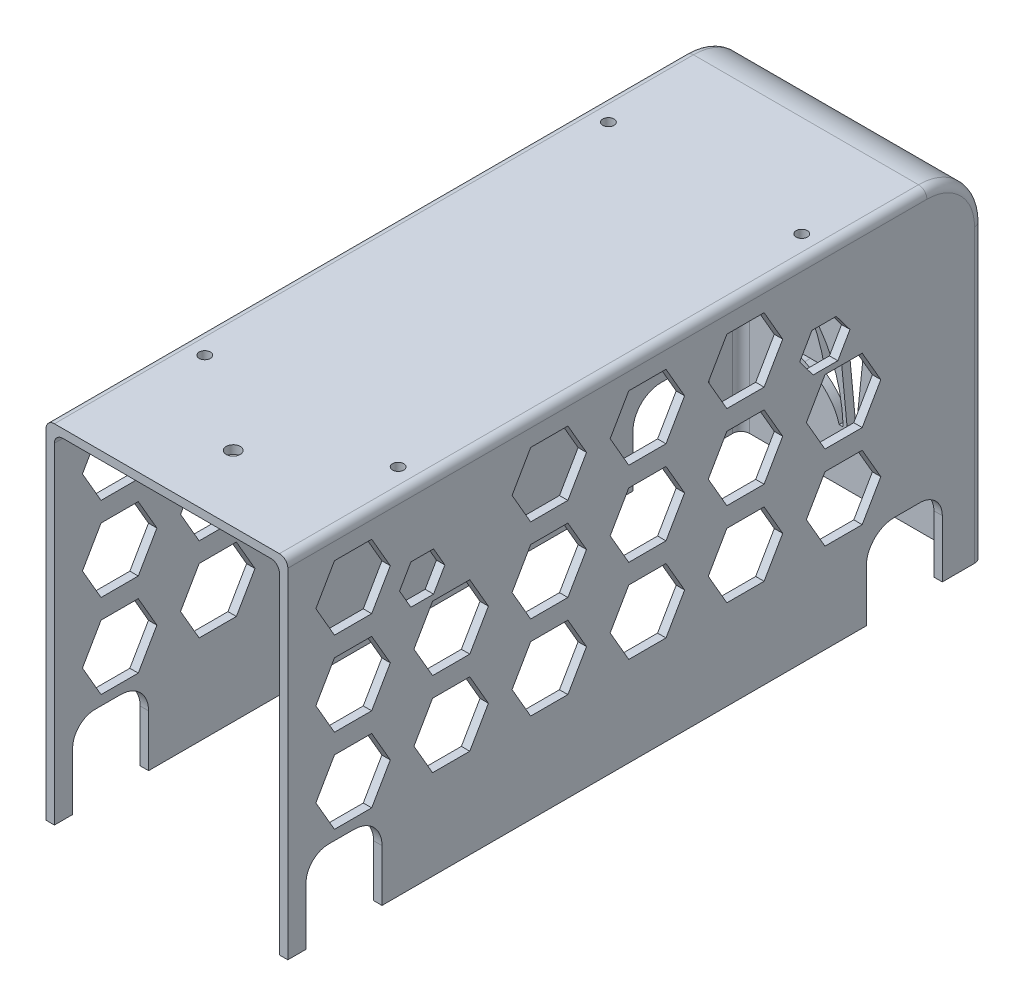
SolidWorks part; units mm, degrees
ref_plane "Front Plane" through (0, 0, 0) normal (0, 0, 1) x (1, 0, 0)
ref_plane "Top Plane" through (0, 0, 0) normal (0, 1, 0) x (1, 0, 0)
ref_plane "Right Plane" through (0, 0, 0) normal (1, 0, 0) x (0, 0, -1)
sketch "Sketch1" plane through (0, 0, 0) normal (1, 0, 0) x (0, 0, -1)
  line L0 (-77.887, -82.1549) -> (77.913, -82.1549)
  line L1 (-124.987, 51.8451) -> (125.013, 51.8451)
  line L2 (-124.987, 51.8451) -> (-124.987, -82.1549)
  line L3 (-124.987, -82.1549) -> (-94.887, -82.1549)
  line L4 (125.013, 51.8451) -> (125.013, -82.1549)
  line L15 (0.013, 51.8451) -> (0.013, -82.1549) construction
  line L16 (94.913, -82.1549) -> (125.013, -82.1549)
  line L17 (-94.887, -82.1549) -> (-77.887, -82.1549) construction
  line L18 (-94.887, -82.1549) -> (-94.887, -78.1549)
  line L20 (-77.887, -78.1549) -> (-77.887, -82.1549)
  line L21 (77.913, -78.1549) -> (77.913, -82.1549)
  line L22 (94.913, -82.1549) -> (94.913, -78.1549)
  circle A6 centre (-101.987, -28.6549) radius 10
  circle A7 centre (102.013, -28.6549) radius 10
  arc A10 (-77.887, -78.1549) -> (-94.887, -78.1549) centre (-86.387, -78.1549) ccw
  arc A11 (77.913, -78.1549) -> (94.913, -78.1549) centre (86.413, -78.1549) cw
  dimension "D3" = 4
  dimension "D7" = 23
  dimension "D8" = 20
  dimension "D9" = 53.5
  dimension "D4" = 17
  dimension "D1" = 250
  dimension "D2" = 134
extrude "Boss-Extrude1" add sketch "Sketch1" against normal blind 3
sketch "Sketch2" plane through (-3, 0, 0) normal (-1, 0, 0) x (0, 0, 1)
  line L0 (-125.013, 51.8451) -> (-72.013, 51.8451) construction
  line L1 (-125.013, 51.8451) -> (124.987, 51.8451) construction
  line L2 (-72.013, 51.8451) -> (-72.013, 59.8451) construction
  line L3 (-0.013, 51.8451) -> (-0.013, -82.1549) construction
  line L4 (-75.013, 59.8451) -> (-69.013, 59.8451)
  line L5 (-76.013, 58.8451) -> (-76.013, 54.8451)
  line L6 (-75.013, 53.8451) -> (-69.013, 53.8451)
  line L7 (-68.013, 58.8451) -> (-68.013, 54.8451)
  line L8 (77.887, -82.1549) -> (-77.913, -82.1549) construction
  line L9 (71.987, 51.8451) -> (71.987, 59.8451) construction
  line L10 (124.987, 51.8451) -> (71.987, 51.8451) construction
  line L11 (67.987, 58.8451) -> (67.987, 54.8451)
  line L12 (74.987, 53.8451) -> (68.987, 53.8451)
  line L13 (75.987, 58.8451) -> (75.987, 54.8451)
  line L14 (74.987, 59.8451) -> (68.987, 59.8451)
  arc A0 (-69.013, 59.8451) -> (-68.013, 58.8451) centre (-69.013, 58.8451) cw
  arc A1 (-69.013, 53.8451) -> (-68.013, 54.8451) centre (-69.013, 54.8451) ccw
  arc A2 (-76.013, 54.8451) -> (-75.013, 53.8451) centre (-75.013, 54.8451) ccw
  arc A3 (-75.013, 59.8451) -> (-76.013, 58.8451) centre (-75.013, 58.8451) ccw
  arc A4 (74.987, 59.8451) -> (75.987, 58.8451) centre (74.987, 58.8451) cw
  arc A5 (75.987, 54.8451) -> (74.987, 53.8451) centre (74.987, 54.8451) cw
  arc A6 (68.987, 53.8451) -> (67.987, 54.8451) centre (68.987, 54.8451) cw
  arc A7 (68.987, 59.8451) -> (67.987, 58.8451) centre (68.987, 58.8451) ccw
  point P10 (-72.013, 59.8451)
  point P17 (-76.013, 53.8451)
  point P20 (-76.013, 59.8451)
  point P40 (75.987, 59.8451)
  point P41 (75.987, 53.8451)
  dimension "D5" = 1
  dimension "D1" = 53
  dimension "D2" = 2
  dimension "D3" = 8
extrude "Boss-Extrude2" add sketch "Sketch2" along normal blind 10
sketch "Sketch3" plane through (0, 59.8451, 0) normal (0, 1, 0) x (1, 0, 0)
  line L3 (-3, 0.013) -> (-19.4349, 0.013) construction
  line L4 (-3, 125.013) -> (-3, -124.987) construction
  line L5 (-13, -71.987) -> (-3, -71.987) construction
  circle A0 centre (-8.6365, 72.013) radius 1.7353
  circle A1 centre (-8.6365, -71.987) radius 1.7353
sketch "Sketch4" plane through (0, 53.8451, 0) normal (0, -1, 0) x (1, 0, 0)
  line L0 (-13, -72.013) -> (-3, -72.013) construction
  line L14 (-13, -75.013) -> (-13, -69.013) construction
  line L15 (-3, -75.013) -> (-3, -69.013) construction
  line L16 (-3, 71.987) -> (-13, 71.987) construction
  line L17 (-3, 68.987) -> (-3, 74.987) construction
  line L18 (-13, 68.987) -> (-13, 74.987) construction
  line L19 (-8.6365, 71.987) -> (-8.6365, -72.013) construction
  circle A1 centre (-8.6365, 71.987) radius 3
  circle A3 centre (-8.6365, -72.013) radius 3
  dimension "D1" = 6
  dimension "D2" = 6
sketch "Sketch5" plane through (0, 0, 0) normal (1, 0, 0) x (0, 0, -1)
  line L1 (-124.987, 51.8451) -> (125.013, 51.8451)
  line L2 (-124.987, 51.8451) -> (-124.987, 76.8451)
  line L10 (0.013, 76.8451) -> (0.013, -82.1549) construction
  line L11 (-77.887, -82.1549) -> (77.913, -82.1549) construction
  line L12 (0.013, -2.6549) -> (173.6231, -2.6549) construction
  line L21 (125.013, 51.8451) -> (125.013, -82.1549)
  line L23 (-124.987, 76.8451) -> (108.013, 76.8451)
  line L24 (128.013, 56.8451) -> (128.013, -82.1549)
  line L25 (128.013, -82.1549) -> (125.013, -82.1549)
  arc A8 (108.013, 76.8451) -> (128.013, 56.8451) centre (108.013, 56.8451) cw
  line M30 (125.013, -82.1549) -> (125.013, 51.8451)
  line M31 (125.013, 51.8451) -> (-124.987, 51.8451)
  dimension "D2" = 3
  dimension "D1" = 20
extrude "Boss-Extrude3" add sketch "Sketch5" against normal up to surface (3 mm away) contours L2 M30 M31 region at (0, 59.429, -7.5021) up to face at (-3, -28.6549, -92.013)
sketch "Sketch6" plane through (0, 76.8451, 0) normal (0, 1, 0) x (1, 0, 0)
  line L2 (-83.2765, 76.013) -> (-73.2765, 76.013) construction
  line L3 (-83.2765, 76.013) -> (-83.2765, 68.9594) construction
  line L4 (-83.2765, 68.9594) -> (-73.2765, 68.9594) construction
  line L5 (-73.2765, 76.013) -> (-73.2765, 68.9594) construction
  line L6 (-13, 76.013) -> (-3, 76.013) construction
  line L7 (-13, 76.013) -> (-13, 68.013) construction
  line L10 (-83.2765, -124.987) -> (-86.2765, -124.987)
  line L14 (-8.6365, 0.013) -> (-65.4749, 0.013) construction
  line L15 (-73.2765, -75.987) -> (-73.2765, -68.9334) construction
  line L16 (-83.2765, -68.9334) -> (-73.2765, -68.9334) construction
  line L17 (-83.2765, -75.987) -> (-83.2765, -68.9334) construction
  line L18 (-83.2765, -75.987) -> (-73.2765, -75.987) construction
  line L19 (-83.2765, 128.013) -> (-86.2765, 128.013)
  line L23 (-83.2765, 128.013) -> (-83.2765, -124.987)
  line L24 (-86.2765, -124.987) -> (-86.2765, 128.013)
  line L26 (-86.2765, 135.013) -> (-113.3718, 135.013) construction
  circle A1 centre (-77.6365, 72.013) radius 1.735 construction
  circle A6 centre (-77.6365, -71.987) radius 1.735 construction
  dimension "D2" = 3.47
  dimension "D3" = 4
  dimension "D4" = 5.64
  dimension "D5" = 10
extrude "Boss-Extrude4" add sketch "Sketch6" against normal up to surface (159 mm away) separate body up to face at (-1.5, -82.1549, -111.463)
sketch "Sketch8" plane through (-83.2765, 0, 0) normal (-1, 0, 0) x (0, 0, 1)
  line L0 (-75.013, 59.8451) -> (-69.013, 59.8451)
  line L1 (-68.013, 58.8451) -> (-68.013, 54.8451)
  line L2 (-69.013, 53.8451) -> (-75.013, 53.8451)
  line L3 (-76.013, 54.8451) -> (-76.013, 58.8451)
  line L4 (68.987, 59.8451) -> (74.987, 59.8451)
  line L5 (75.987, 58.8451) -> (75.987, 54.8451)
  line L6 (74.987, 53.8451) -> (68.987, 53.8451)
  line L7 (67.987, 54.8451) -> (67.987, 58.8451)
  arc A0 (-69.013, 59.8451) -> (-68.013, 58.8451) centre (-69.013, 58.8451) cw
  arc A1 (-68.013, 54.8451) -> (-69.013, 53.8451) centre (-69.013, 54.8451) cw
  arc A2 (-75.013, 53.8451) -> (-76.013, 54.8451) centre (-75.013, 54.8451) cw
  arc A3 (-76.013, 58.8451) -> (-75.013, 59.8451) centre (-75.013, 58.8451) cw
  arc A4 (74.987, 59.8451) -> (75.987, 58.8451) centre (74.987, 58.8451) cw
  arc A5 (75.987, 54.8451) -> (74.987, 53.8451) centre (74.987, 54.8451) cw
  arc A6 (68.987, 53.8451) -> (67.987, 54.8451) centre (68.987, 54.8451) cw
  arc A7 (67.987, 58.8451) -> (68.987, 59.8451) centre (68.987, 58.8451) cw
extrude "Boss-Extrude6" add sketch "Sketch8" against normal blind 10
sketch "Sketch9" plane through (0, 59.8451, 0) normal (0, 1, 0) x (1, 0, 0)
  line L0 (-83.2765, 72.013) -> (-3, 72.013) construction
  line L1 (-83.2765, 69.013) -> (-83.2765, 75.013) construction
  line L2 (-3, 69.013) -> (-3, 75.013) construction
  line L3 (-43.1383, 72.013) -> (-43.1383, -18.9939) construction
  circle A0 centre (-77.6365, -71.987) radius 1.735
  circle A1 centre (-77.6365, 72.013) radius 1.735
  circle A2 centre (-8.64, -71.987) radius 1.735
  circle A3 centre (-8.64, 72.013) radius 1.735
  dimension "D1" = 3.47
extrude "Cut-Extrude3" cut sketch "Sketch9" against normal blind 10
sketch "Sketch11" plane through (-3, 0, 0) normal (-1, 0, 0) x (0, 0, 1)
  line L5 (124.987, 73.8451) -> (124.987, 76.8451)
  line L6 (-125.013, -82.1549) -> (-128.013, -82.1549)
  line L7 (-125.013, 56.8451) -> (-125.013, -82.1549)
  line L8 (124.987, 73.8451) -> (-108.013, 73.8451)
  line L9 (-125.013, 56.8451) -> (-125.013, -82.1549)
  line L10 (124.987, 73.8451) -> (-108.013, 73.8451)
  line L11 (-128.013, -82.1549) -> (-128.013, 56.8451)
  line L12 (-108.013, 76.8451) -> (124.987, 76.8451)
  arc A2 (-128.013, 56.8451) -> (-108.013, 76.8451) centre (-108.013, 56.8451) cw
  arc A3 (-108.013, 73.8451) -> (-125.013, 56.8451) centre (-108.013, 56.8451) ccw
  arc A4 (-108.013, 73.8451) -> (-125.013, 56.8451) centre (-108.013, 56.8451) ccw
  dimension "D1" = 3
extrude "Boss-Extrude7" add sketch "Sketch11" along normal up to surface (80.2765 mm away) up to face at (-83.2765, 56.8451, 71.987)
sketch "Sketch13" plane through (0, 0, 0) normal (1, 0, 0) x (0, 0, -1)
  line L0 (-111.987, -28.6549) -> (-111.987, -82.1549)
  line L1 (-124.987, -82.1549) -> (-94.887, -82.1549) construction
  line L7 (94.913, -82.1549) -> (128.013, -82.1549) construction
  line L8 (112.013, -82.1549) -> (112.013, -28.6549)
  line L10 (-77.887, -78.1549) -> (-77.887, -82.1549) construction
  line L16 (-101.987, -18.6549) -> (-96.387, -18.6549)
  line L17 (-86.387, -28.6549) -> (-86.387, -69.6549)
  line L18 (102.013, -18.6549) -> (96.413, -18.6549)
  line L19 (86.413, -28.6549) -> (86.413, -69.6549)
  line L21 (-77.887, -78.1549) -> (-77.887, -82.1549)
  line L22 (-77.887, -82.1549) -> (-111.987, -82.1549)
  line L24 (77.913, -78.1549) -> (77.913, -82.1549)
  line L25 (-124.987, -82.1549) -> (125.013, -82.1549) construction
  line L26 (77.913, -82.1549) -> (112.013, -82.1549)
  arc A0 (-101.987, -18.6549) -> (-111.987, -28.6549) centre (-101.987, -28.6549) ccw
  arc A1 (112.013, -28.6549) -> (102.013, -18.6549) centre (102.013, -28.6549) ccw
  arc A2 (-86.387, -69.6549) -> (-77.887, -78.1549) centre (-86.387, -78.1549) cw
  arc A3 (77.913, -78.1549) -> (86.413, -69.6549) centre (86.413, -78.1549) cw
  arc A4 (-96.387, -18.6549) -> (-86.387, -28.6549) centre (-96.387, -28.6549) cw
  arc A5 (96.413, -18.6549) -> (86.413, -28.6549) centre (96.413, -28.6549) ccw
  dimension "D1" = 10
  dimension "D2" = 10
extrude "Cut-Extrude6" cut sketch "Sketch13" against normal blind 143
sketch "Sketch14" plane through (0, 0, 0) normal (1, 0, 0) x (0, 0, -1)
  line L1 (-124.987, -82.1549) -> (128.013, -82.1549)
  line L2 (-124.987, -82.1549) -> (-124.987, -47.1549)
  line L7 (-124.987, -47.1549) -> (128.013, -47.1549)
  line L8 (128.013, -82.1549) -> (128.013, -47.1549)
  line L9 (128.013, 56.8451) -> (128.013, -82.1549) construction
  dimension "D1" = 35
extrude "Cut-Extrude7" cut sketch "Sketch14" against normal blind 143
sketch "Sketch15" plane through (0, 0, 0) normal (1, 0, 0) x (0, 0, -1)
  line L8 (108.013, 76.8451) -> (128.013, 76.8451)
  line L9 (128.013, 76.8451) -> (128.013, 56.8451)
  line L14 (128.013, 56.8451) -> (128.013, -47.1549) construction
  line L15 (128.013, 56.8451) -> (128.013, 76.8451) construction
  arc A1 (128.013, 56.8451) -> (108.013, 76.8451) centre (108.013, 56.8451) ccw
extrude "Cut-Extrude8" cut sketch "Sketch15" against normal blind 143
fillet "Fillet3" radius 3 3 edges at (0, 4.8451, -128.013) (0, 70.9872, -122.1551) (0, 76.8451, 8.487)
fillet "Fillet4" radius 3 3 edges at (-86.2765, 76.8451, 8.487) (-86.2765, 4.8451, -128.013) (-86.2765, 70.9872, -122.1551)
fillet "Fillet5" radius 3 6 edges at (-3, 4.8451, -125.013) (-3, 68.8659, -120.0338) (-83.2765, 4.8451, -125.013) (-83.2765, 68.8659, -120.0338) (-3, 73.8451, 8.487) (-83.2765, 73.8451, 8.487)
sketch "Sketch17" plane through (0, 76.8451, 0) normal (0, 1, 0) x (1, 0, 0)
  circle A3 centre (-43.1388, -96.337) radius 2.5
  dimension "D6" = 5
extrude "Cut-Extrude9" cut sketch "Sketch17" against normal blind 143
sketch "Sketch18" plane through (0, 0, 0) normal (1, 0, 0) x (0, 0, -1)
  line L1 (-132.5686, 81.0343) -> (-119.987, 81.0343)
  line L2 (-132.5686, 81.0343) -> (-132.5686, -50.9934)
  line L3 (-132.5686, -50.9934) -> (-119.987, -50.9934)
  line L4 (-119.987, 81.0343) -> (-119.987, -50.9934)
extrude "Cut-Extrude10" cut sketch "Sketch18" against normal blind 143
sketch "Sketch21" plane through (0, 0, -128.013) normal (0, 0, -1) x (-1, 0, 0)
  line L0 (3, 56.8451) -> (3, -47.1549) construction
  line L1 (83.2765, -47.1549) -> (83.2765, 56.8451) construction
  arc A0 (3, 23.6188) -> (83.2765, 23.6188) centre (43.1383, -11.0736) cw construction
  text T0 "SOKA UNVERSITY" font "Arial Narrow" height in points 26
extrude "Cut-Extrude11" cut sketch "Sketch21" against normal blind 143
sketch "Sketch22" plane through (0, 0, -128.013) normal (0, 0, -1) x (-1, 0, 0)
  line L0 (-62.3867, -52.9922) -> (58.1402, -52.9922) construction
  line L1 (42.401, -28.4273) -> (45.401, -28.4273)
  line L2 (45.401, -28.4273) -> (48.0456, -3.2659)
  line L3 (48.0456, -3.2659) -> (45.049, 3.6095)
  line L7 (42.7531, 3.6095) -> (39.7564, -3.2659)
  line L8 (39.7564, -3.2659) -> (42.401, -28.4273)
  line L9 (53.5774, -13.0804) -> (67.6449, -13.0804)
  line L10 (43.901, -28.4273) -> (43.901, -11.0471) construction
  line L11 (34.2246, -13.0804) -> (20.1572, -13.0804)
  line L12 (39.501, -28.4313) -> (40.901, -28.4313)
  line L13 (46.901, -28.4313) -> (48.301, -28.4313)
  line L14 (42.7531, 3.6095) -> (42.7531, -3.2659)
  line L15 (42.7531, -3.2659) -> (45.049, -3.2659)
  line L16 (45.049, -3.2659) -> (45.049, 3.6095)
  spline S0 degree 2 poles (46.901, -28.4313) (47.5698, -7.863) (60.5702, 3.7997) knots 0 0 0 0.93281 0.93281 0.93281
  spline S1 degree 2 poles (53.5774, -13.0804) (55.4552, -3.7048) (60.5702, 3.7997) knots 0 0 0 0.781227 0.781227 0.781227
  spline S2 degree 2 poles (60.5702, -15.1027) (50.4261, -20.3332) (48.301, -28.4313) knots 0 0 0 0.602451 0.602451 0.602451
  spline S3 degree 2 poles (60.5702, -15.1027) (63.6901, -13.6555) (67.6449, -13.0804) knots 0 0 0 0.667088 0.667088 0.667088
  spline S4 degree 2 poles (27.2319, -15.1027) (37.3759, -20.3332) (39.501, -28.4313) knots 0 0 0 0.602451 0.602451 0.602451
  spline S5 degree 2 poles (27.2319, -15.1027) (24.112, -13.6555) (20.1572, -13.0804) knots 0 0 0 0.667088 0.667088 0.667088
  spline S6 degree 2 poles (34.2246, -13.0804) (32.3469, -3.7048) (27.2319, 3.7997) knots 0 0 0 0.781227 0.781227 0.781227
  spline S7 degree 2 poles (40.901, -28.4313) (40.2322, -7.863) (27.2319, 3.7997) knots 0 0 0 0.93281 0.93281 0.93281
  dimension "D1" = 84
  dimension "D2" = 84
  dimension "D3" = 3
  dimension "D4" = 1.5
  dimension "D5" = 1.4
  dimension "D6" = 25.3
  dimension "D7" = 25.3
  dimension "D8" = 7.5
  dimension "D9" = 7.5
  dimension "D10" = 150.45
  dimension "D11" = 150.45
extrude "Cut-Extrude12" cut sketch "Sketch22" against normal blind 143
sketch "Sketch23" plane through (0, 0, 0) normal (1, 0, 0) x (0, 0, -1)
  line L0 (-111.987, -47.1549) -> (-113.487, -47.1549)
  line L1 (-111.987, -47.1549) -> (-119.987, -47.1549) construction
  line L2 (-113.487, -47.1549) -> (-113.487, -26.6549)
  line L3 (-105.487, -18.6549) -> (-101.987, -18.6549)
  line L4 (-101.987, -18.6549) -> (-101.987, -47.1549)
  line L5 (-101.987, -47.1549) -> (-111.987, -47.1549)
  line L6 (0.013, -47.1549) -> (0.013, -16.2542) construction
  line L7 (86.413, -47.1549) -> (-86.387, -47.1549) construction
  line L8 (102.013, -47.1549) -> (112.013, -47.1549)
  line L9 (102.013, -18.6549) -> (102.013, -47.1549)
  line L10 (105.513, -18.6549) -> (102.013, -18.6549)
  line L11 (113.513, -47.1549) -> (113.513, -26.6549)
  line L12 (112.013, -47.1549) -> (113.513, -47.1549)
  arc A0 (-113.487, -26.6549) -> (-105.487, -18.6549) centre (-105.487, -26.6549) cw
  arc A1 (113.513, -26.6549) -> (105.513, -18.6549) centre (105.513, -26.6549) ccw
  dimension "D2" = 8
  dimension "D1" = 1.5
extrude "Cut-Extrude13" cut sketch "Sketch23" against normal through all
sketch "Sketch24" plane through (0, 73.8451, 0) normal (0, -1, 0) x (1, 0, 0)
  circle A0 centre (-77.6365, 71.987) radius 2
  circle A1 centre (-8.64, 71.987) radius 2
  circle A2 centre (-8.64, -72.013) radius 2
  circle A3 centre (-77.6365, -72.013) radius 2
  circle A4 centre (-77.6365, -72.013) radius 3
  circle A5 centre (-8.64, -72.013) radius 3
  circle A6 centre (-8.64, 71.987) radius 3
  circle A7 centre (-77.6365, 71.987) radius 3
  dimension "D1" = 6
  dimension "D2" = 4
extrude "Boss-Extrude8" add sketch "Sketch24" along normal up to surface (14 mm away) up to face at (-77.6365, 59.8451, 73.722)
sketch "Sketch25" plane through (0, 73.8451, 0) normal (0, -1, 0) x (1, 0, 0)
  circle A0 centre (-8.64, 71.987) radius 2
  circle A1 centre (-77.6365, 71.987) radius 2
  circle A2 centre (-8.64, -72.013) radius 2
  circle A3 centre (-77.6365, -72.013) radius 2
  dimension "D1" = 4
  dimension "D2" = 4
extrude "Cut-Extrude14" cut sketch "Sketch25" against normal blind 10
sketch "Sketch26" plane through (0, 0, 0) normal (1, 0, 0) x (0, 0, -1)
  line L0 (108.013, 73.8451) -> (-119.987, 73.8451) construction
  line L1 (-83.4289, 56.3451) -> (-90.0684, 67.8451)
  line L2 (-90.0684, 67.8451) -> (-103.3475, 67.8451)
  line L3 (-103.3475, 67.8451) -> (-109.987, 56.3451)
  line L4 (-109.987, 56.3451) -> (-103.3475, 44.8451)
  line L5 (-103.3475, 44.8451) -> (-90.0684, 44.8451)
  line L6 (-90.0684, 44.8451) -> (-83.4289, 56.3451)
  line L7 (-119.987, -47.1549) -> (-119.987, 73.8451) construction
  line L14 (-33.3475, 67.8451) -> (-39.987, 56.3451)
  line L15 (-20.0684, 67.8451) -> (-33.3475, 67.8451)
  line L16 (-13.4289, 56.3451) -> (-20.0684, 67.8451)
  line L17 (-20.0684, 44.8451) -> (-13.4289, 56.3451)
  line L18 (-33.3475, 44.8451) -> (-20.0684, 44.8451)
  line L19 (-39.987, 56.3451) -> (-33.3475, 44.8451)
  line L20 (1.6525, 67.8451) -> (-4.987, 56.3451)
  line L21 (14.9316, 67.8451) -> (1.6525, 67.8451)
  line L22 (21.5711, 56.3451) -> (14.9316, 67.8451)
  line L23 (14.9316, 44.8451) -> (21.5711, 56.3451)
  line L24 (1.6525, 44.8451) -> (14.9316, 44.8451)
  line L25 (-4.987, 56.3451) -> (1.6525, 44.8451)
  line L26 (36.6525, 67.8451) -> (30.013, 56.3451)
  line L27 (49.9316, 67.8451) -> (36.6525, 67.8451)
  line L28 (56.5711, 56.3451) -> (49.9316, 67.8451)
  line L29 (49.9316, 44.8451) -> (56.5711, 56.3451)
  line L30 (36.6525, 44.8451) -> (49.9316, 44.8451)
  line L31 (30.013, 56.3451) -> (36.6525, 44.8451)
  line L38 (-68.3475, 37.8451) -> (-74.987, 26.3451)
  line L39 (-55.0684, 37.8451) -> (-68.3475, 37.8451)
  line L40 (-48.4289, 26.3451) -> (-55.0684, 37.8451)
  line L41 (-55.0684, 14.8451) -> (-48.4289, 26.3451)
  line L42 (-68.3475, 14.8451) -> (-55.0684, 14.8451)
  line L43 (-74.987, 26.3451) -> (-68.3475, 14.8451)
  line L44 (-33.3475, 37.8451) -> (-39.987, 26.3451)
  line L45 (-20.0684, 37.8451) -> (-33.3475, 37.8451)
  line L46 (-13.4289, 26.3451) -> (-20.0684, 37.8451)
  line L47 (-20.0684, 14.8451) -> (-13.4289, 26.3451)
  line L48 (-33.3475, 14.8451) -> (-20.0684, 14.8451)
  line L49 (-39.987, 26.3451) -> (-33.3475, 14.8451)
  line L50 (1.6525, 37.8451) -> (-4.987, 26.3451)
  line L51 (14.9316, 37.8451) -> (1.6525, 37.8451)
  line L52 (21.5711, 26.3451) -> (14.9316, 37.8451)
  line L53 (14.9316, 14.8451) -> (21.5711, 26.3451)
  line L54 (1.6525, 14.8451) -> (14.9316, 14.8451)
  line L55 (-4.987, 26.3451) -> (1.6525, 14.8451)
  line L56 (36.6525, 37.8451) -> (30.013, 26.3451)
  line L57 (49.9316, 37.8451) -> (36.6525, 37.8451)
  line L58 (56.5711, 26.3451) -> (49.9316, 37.8451)
  line L59 (49.9316, 14.8451) -> (56.5711, 26.3451)
  line L60 (36.6525, 14.8451) -> (49.9316, 14.8451)
  line L61 (30.013, 26.3451) -> (36.6525, 14.8451)
  line L62 (71.6525, 37.8451) -> (65.013, 26.3451)
  line L63 (84.9316, 37.8451) -> (71.6525, 37.8451)
  line L64 (91.5711, 26.3451) -> (84.9316, 37.8451)
  line L65 (84.9316, 14.8451) -> (91.5711, 26.3451)
  line L66 (71.6525, 14.8451) -> (84.9316, 14.8451)
  line L67 (65.013, 26.3451) -> (71.6525, 14.8451)
  line L68 (-68.3475, 7.8451) -> (-74.987, -3.6549)
  line L69 (-55.0684, 7.8451) -> (-68.3475, 7.8451)
  line L70 (-48.4289, -3.6549) -> (-55.0684, 7.8451)
  line L71 (-55.0684, -15.1549) -> (-48.4289, -3.6549)
  line L72 (-68.3475, -15.1549) -> (-55.0684, -15.1549)
  line L73 (-74.987, -3.6549) -> (-68.3475, -15.1549)
  line L74 (-33.3475, 7.8451) -> (-39.987, -3.6549)
  line L75 (-20.0684, 7.8451) -> (-33.3475, 7.8451)
  line L76 (-13.4289, -3.6549) -> (-20.0684, 7.8451)
  line L77 (-20.0684, -15.1549) -> (-13.4289, -3.6549)
  line L78 (-33.3475, -15.1549) -> (-20.0684, -15.1549)
  line L79 (-39.987, -3.6549) -> (-33.3475, -15.1549)
  line L80 (1.6525, 7.8451) -> (-4.987, -3.6549)
  line L81 (14.9316, 7.8451) -> (1.6525, 7.8451)
  line L82 (21.5711, -3.6549) -> (14.9316, 7.8451)
  line L83 (14.9316, -15.1549) -> (21.5711, -3.6549)
  line L84 (1.6525, -15.1549) -> (14.9316, -15.1549)
  line L85 (-4.987, -3.6549) -> (1.6525, -15.1549)
  line L86 (36.6525, 7.8451) -> (30.013, -3.6549)
  line L87 (49.9316, 7.8451) -> (36.6525, 7.8451)
  line L88 (56.5711, -3.6549) -> (49.9316, 7.8451)
  line L89 (49.9316, -15.1549) -> (56.5711, -3.6549)
  line L90 (36.6525, -15.1549) -> (49.9316, -15.1549)
  line L91 (30.013, -3.6549) -> (36.6525, -15.1549)
  line L92 (71.6525, 7.8451) -> (65.013, -3.6549)
  line L93 (84.9316, 7.8451) -> (71.6525, 7.8451)
  line L94 (91.5711, -3.6549) -> (84.9316, 7.8451)
  line L95 (84.9316, -15.1549) -> (91.5711, -3.6549)
  line L96 (71.6525, -15.1549) -> (84.9316, -15.1549)
  line L97 (65.013, -3.6549) -> (71.6525, -15.1549)
  line L98 (-103.3475, 37.8451) -> (-109.987, 26.3451)
  line L99 (-90.0684, 37.8451) -> (-103.3475, 37.8451)
  line L100 (-83.4289, 26.3451) -> (-90.0684, 37.8451)
  line L101 (-90.0684, 14.8451) -> (-83.4289, 26.3451)
  line L102 (-103.3475, 14.8451) -> (-90.0684, 14.8451)
  line L103 (-109.987, 26.3451) -> (-103.3475, 14.8451)
  line L104 (-103.3475, 7.8451) -> (-109.987, -3.6549)
  line L105 (-90.0684, 7.8451) -> (-103.3475, 7.8451)
  line L106 (-83.4289, -3.6549) -> (-90.0684, 7.8451)
  line L107 (-90.0684, -15.1549) -> (-83.4289, -3.6549)
  line L108 (-103.3475, -15.1549) -> (-90.0684, -15.1549)
  line L109 (-109.987, -3.6549) -> (-103.3475, -15.1549)
  line L110 (-68.3475, 44.8451) -> (-55.0684, 44.8451) [skipped]
  line L111 (-55.0684, 44.8451) -> (-48.4289, 56.3451) [skipped]
  line L112 (-48.4289, 56.3451) -> (-55.0684, 67.8451) [skipped]
  line L113 (-55.0684, 67.8451) -> (-68.3475, 67.8451) [skipped]
  line L114 (-68.3475, 67.8451) -> (-74.987, 56.3451) [skipped]
  line L115 (-74.987, 56.3451) -> (-68.3475, 44.8451) [skipped]
  line L116 (65.013, 56.3451) -> (71.6525, 44.8451) [skipped]
  line L117 (71.6525, 67.8451) -> (65.013, 56.3451) [skipped]
  line L118 (84.9316, 67.8451) -> (71.6525, 67.8451) [skipped]
  line L119 (91.5711, 56.3451) -> (84.9316, 67.8451) [skipped]
  line L120 (84.9316, 44.8451) -> (91.5711, 56.3451) [skipped]
  line L121 (71.6525, 44.8451) -> (84.9316, 44.8451) [skipped]
  circle A0 centre (-96.708, 56.3451) radius 11.5 construction
  dimension "D1" = 6
  dimension "D2" = 23
  dimension "D3" = 10
  dimension "D4" = 6
  dimension "D5" = 3
extrude "Cut-Extrude15" cut sketch "Sketch26" against normal blind 105
sketch "Sketch27" plane through (0, 0, 0) normal (-1, 0, 0) x (0, 0, 1)
  line L0 (74.987, 53.8451) -> (68.987, 53.8451) construction
  line L1 (80.1246, 46.8451) -> (76.0831, 53.8451)
  line L2 (76.0831, 53.8451) -> (68.0002, 53.8451)
  line L3 (68.0002, 53.8451) -> (63.9588, 46.8451)
  line L4 (63.9588, 46.8451) -> (68.0002, 39.8451)
  line L5 (68.0002, 39.8451) -> (76.0831, 39.8451)
  line L6 (76.0831, 39.8451) -> (80.1246, 46.8451)
  line L7 (-62.6151, 46.2384) -> (-67.0069, 53.8451)
  line L8 (-67.0069, 53.8451) -> (-75.6671, 53.8451)
  line L9 (-75.6671, 53.8451) -> (-80.5746, 47.3451)
  line L10 (-80.5746, 47.3451) -> (-76.2445, 39.8451)
  line L11 (-76.2445, 39.8451) -> (-67.442, 39.8451)
  line L12 (-67.442, 39.8451) -> (-62.6151, 46.2384)
  line L13 (-69.013, 53.8451) -> (-75.013, 53.8451) construction
  circle A0 centre (72.0417, 46.8451) radius 7 construction
  circle A1 centre (-71.9144, 47.3451) radius 7.5 construction
  dimension "D1" = 14
  dimension "D2" = 14
  dimension "D3" = 15
  dimension "D4" = 15
  dimension "D5" = 8.6603
extrude "Cut-Extrude16" cut sketch "Sketch27" along normal blind 105
sketch "Sketch28" plane through (0, 59.8451, 0) normal (0, 1, 0) x (1, 0, 0)
  circle A0 centre (-77.6365, 72.013) radius 2
  circle A1 centre (-8.64, 72.013) radius 2
  circle A2 centre (-8.64, -71.987) radius 2
  circle A3 centre (-77.6365, -71.987) radius 2
extrude "Cut-Extrude17" cut sketch "Sketch28" against normal blind 3
